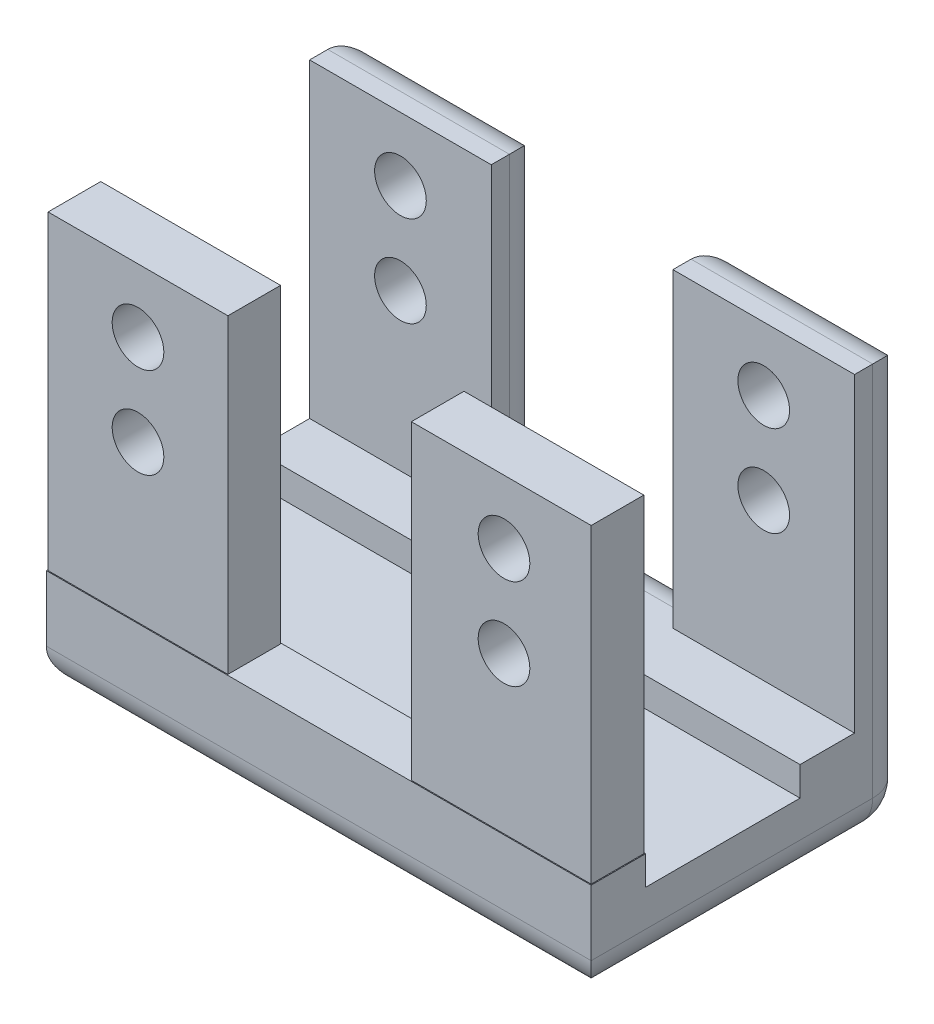
SolidWorks part; units mm, degrees
ref_plane "Front Plane" through (0, 0, 0) normal (0, 0, 1) x (1, 0, 0)
ref_plane "Top Plane" through (0, 0, 0) normal (0, 1, 0) x (1, 0, 0)
ref_plane "Right Plane" through (0, 0, 0) normal (1, 0, 0) x (0, 0, -1)
sketch "Sketch1" plane through (0, 0, 0) normal (0, 1, 0) x (1, 0, 0)
  line L1 (0, 0) -> (30, 0)
  line L2 (0, 0) -> (0, 17.5)
  line L3 (0, 17.5) -> (30, 17.5)
  line L4 (30, 0) -> (30, 17.5)
  dimension "D1" = 30
  dimension "D2" = 17.5
extrude "Boss-Extrude1" add sketch "Sketch1" along normal blind 4
sketch "Sketch2" plane through (0, 4, 0) normal (0, 1, 0) x (1, 0, 0)
  line L0 (30, 0) -> (30, 17.5) construction
  line L1 (0, 17.5) -> (30, 17.5)
  line L2 (0, 17.5) -> (0, 11.5)
  line L3 (0, 11.5) -> (30, 11.5)
  line L4 (30, 17.5) -> (30, 11.5)
  dimension "D1" = 6
extrude "Boss-Extrude2" add sketch "Sketch2" along normal blind 1.601
sketch "Sketch3" plane through (0, 4, 0) normal (0, 1, 0) x (1, 0, 0)
  line L1 (0, 0) -> (10, 0)
  line L2 (0, 0) -> (0, 3)
  line L3 (0, 3) -> (10, 3)
  line L4 (10, 0) -> (10, 3)
  line L5 (30, 0) -> (20, 0)
  line L6 (30, 0) -> (30, 3)
  line L7 (30, 3) -> (20, 3)
  line L8 (20, 0) -> (20, 3)
  dimension "D1" = 10
  dimension "D2" = 3
extrude "Boss-Extrude3" add sketch "Sketch3" along normal blind 18.7
sketch "Sketch4" plane through (0, 5.601, 0) normal (0, 1, 0) x (1, 0, 0)
  line L1 (0, 17.5) -> (10, 17.5)
  line L2 (0, 17.5) -> (0, 14.5)
  line L3 (0, 14.5) -> (10, 14.5)
  line L4 (10, 17.5) -> (10, 14.5)
  line L5 (30, 17.5) -> (20, 17.5)
  line L6 (30, 17.5) -> (30, 14.5)
  line L7 (30, 14.5) -> (20, 14.5)
  line L8 (20, 17.5) -> (20, 14.5)
  dimension "D1" = 10
  dimension "D2" = 3
extrude "Boss-Extrude4" add sketch "Sketch4" along normal blind 17.099
sketch "Sketch5" plane through (0, 4, 0) normal (0, 1, 0) x (1, 0, 0)
  line L1 (10, 3) -> (20, 3)
  line L2 (10, 3) -> (10, 0)
  line L3 (10, 0) -> (20, 0)
  line L4 (20, 3) -> (20, 0)
extrude "Boss-Extrude5" add sketch "Sketch5" along normal blind 1.601
fillet "Fillet1" radius 2 11 edges at (30, 11.35, -17.5) (25, 22.7, -17.5) (20, 14.1505, -17.5) (15, 5.601, -17.5) (10, 14.1505, -17.5) (5, 22.7, -17.5) (0, 11.35, -17.5) (15, 0, 0) (30, 0, -8.75) (15, 0, -17.5) (0, 0, -8.75)
sketch "Sketch6" plane through (0, 0, -14.5) normal (0, 0, 1) x (1, 0, 0)
  line L0 (0, 22.7) -> (10, 22.7) construction
  line L1 (10, 22.7) -> (20, 22.7) construction
  line L2 (15, 22.7) -> (15, 17.0758) construction
  line L3 (5, 22.7) -> (5, 19.2) construction
  circle A0 centre (5, 19.2) radius 1.4224
  circle A1 centre (25, 19.2) radius 1.4224
  circle A2 centre (5, 14.2) radius 1.4224
  circle A3 centre (25, 14.2) radius 1.4224
  dimension "D1" = 2.8448
  dimension "D2" = 3.5
  dimension "D3" = 2
extrude "Cut-Extrude1" cut sketch "Sketch6" against normal up to next
sketch "Sketch7" plane through (0, 0, -3) normal (0, 0, -1) x (-1, 0, 0)
  line L0 (0, 22.7) -> (-10, 22.7) construction
  line L1 (-10, 22.7) -> (-20, 22.7) construction
  line L2 (-15.0754, 22.7) -> (-15.0754, 19.6857) construction
  line L3 (-5, 22.7) -> (-5, 19.2) construction
  circle A0 centre (-5, 19.2) radius 1.4224
  circle A1 centre (-25.1507, 19.2) radius 1.4224
  circle A2 centre (-25.1507, 14.2) radius 1.4224
  circle A3 centre (-5, 14.2) radius 1.4224
  dimension "D1" = 2.8448
  dimension "D2" = 3.5
  dimension "D3" = 2
extrude "Cut-Extrude2" cut sketch "Sketch7" against normal up to next
sketch "Sketch9" plane through (0, 22.7, 0) normal (0, 1, 0) x (1, 0, 0)
  line L0 (25, 0) -> (25, 0.05) construction
  line L1 (30, 0) -> (20, 0)
  line L2 (30, 0) -> (30, 3)
  line L3 (30, 3) -> (20, 3)
  line L4 (20, 0) -> (20, 3)
  line L5 (29.95, 0.05) -> (20.05, 0.05)
  line L6 (29.95, 0.05) -> (29.95, 2.95)
  line L7 (29.95, 2.95) -> (20.05, 2.95)
  line L8 (20.05, 0.05) -> (20.05, 2.95)
  line L9 (10, 0) -> (0, 0)
  line L10 (10, 0) -> (10, 3)
  line L11 (10, 3) -> (0, 3)
  line L12 (0, 0) -> (0, 3)
  line L13 (9.95, 0.05) -> (0.05, 0.05)
  line L14 (9.95, 0.05) -> (9.95, 2.95)
  line L15 (9.95, 2.95) -> (0.05, 2.95)
  line L16 (0.05, 0.05) -> (0.05, 2.95)
  line L17 (30, 1.5) -> (29.95, 1.5) construction
  line L18 (10, 1.5) -> (9.95, 1.5) construction
  line L19 (5, 0) -> (5, 0.05) construction
  dimension "D1" = 2.9
  dimension "D2" = 9.9
  dimension "D3" = 0.05
  dimension "D4" = 0.05
extrude "Cut-Extrude3" cut sketch "Sketch9" against normal up to surface (17.099 mm away) up to face at (15, 5.601, -1.5)
